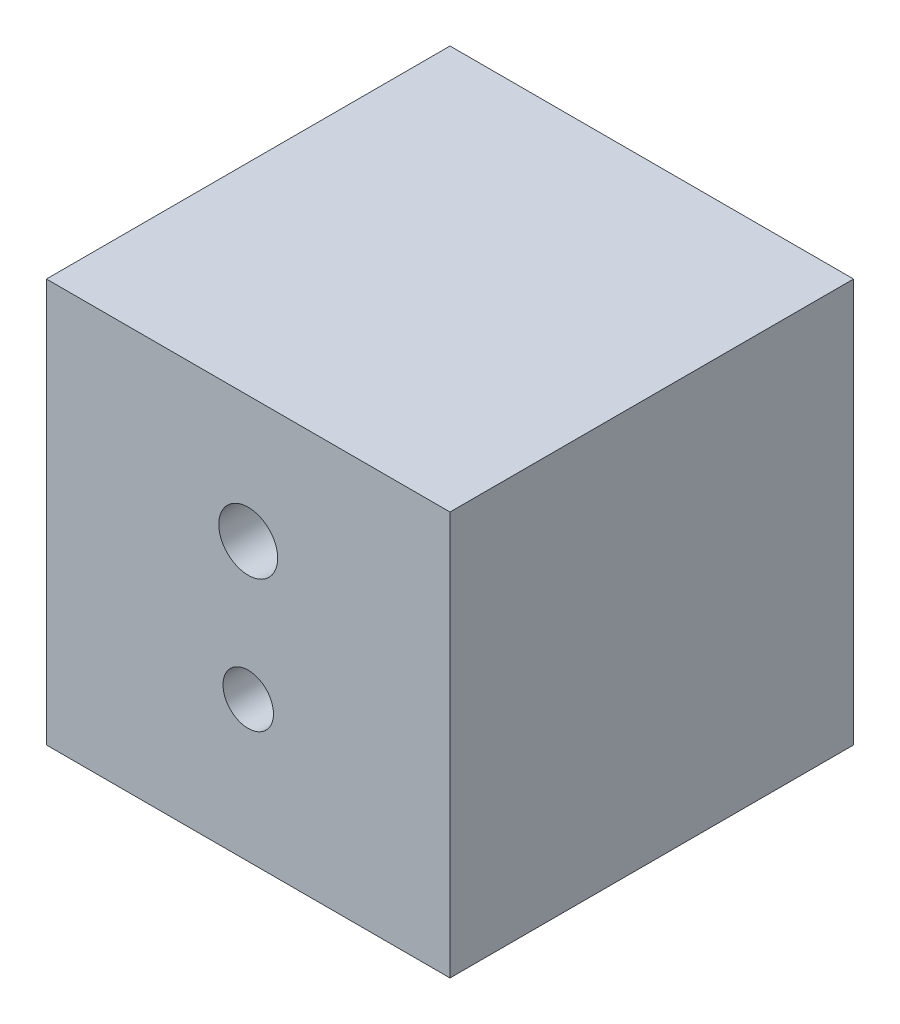
SolidWorks part; units mm, degrees
ref_plane "Front Plane" through (0, 0, 0) normal (0, 0, 1) x (1, 0, 0)
ref_plane "Top Plane" through (0, 0, 0) normal (0, 1, 0) x (1, 0, 0)
ref_plane "Right Plane" through (0, 0, 0) normal (1, 0, 0) x (0, 0, -1)
sketch "Sketch2" plane through (0, 0, 0) normal (0, 1, 0) x (1, 0, 0)
  line L1 (-38.1, -38.1) -> (38.1, -38.1)
  line L2 (-38.1, -38.1) -> (-38.1, 38.1)
  line L3 (-38.1, 38.1) -> (38.1, 38.1)
  line L4 (38.1, -38.1) -> (38.1, 38.1)
  line L5 (-38.1, -38.1) -> (38.1, 38.1) construction
  line L6 (-38.1, 38.1) -> (38.1, -38.1) construction
  point P0 (0, 0)
  dimension "D1" = 76.2
  dimension "D2" = 76.2
extrude "Boss-Extrude1" add sketch "Sketch2" along normal blind 76.2
sketch "Sketch3" plane through (0, 0, 38.1) normal (0, 0, 1) x (1, 0, 0)
  line L2 (0, 52.367) -> (0, 26.5225) construction
  line L3 (-38.1, 0) -> (38.1, 0) construction
  circle A0 centre (0, 26.5225) radius 4.7625
  circle A1 centre (0, 52.367) radius 5.5626
  point P2 (0, 52.367)
  point P4 (0, 39.4448)
  point P6 (14.4652, 63.5)
  point P7 (0, 0)
  point P11 (0, 12.2555)
  dimension "D1" = 9.525
  dimension "D3" = 25.8445
  dimension "D4" = 11.1252
extrude "Cut-Extrude1" cut sketch "Sketch3" against normal blind 72.39
sketch "Sketch4" plane through (0, 0, 38.1) normal (0, 0, 1) x (1, 0, 0)
  line L0 (0, 52.367) -> (0, 26.5225) construction
  circle A0 centre (0, 27.7925) radius 2.4023
  point P4 (0, 0)
  dimension "D1" = 24.5745
equation "\"D1@Sketch2\"=\"D2@Sketch2\""
equation "\"D1@Boss-Extrude1\"=\"D2@Sketch2\""
